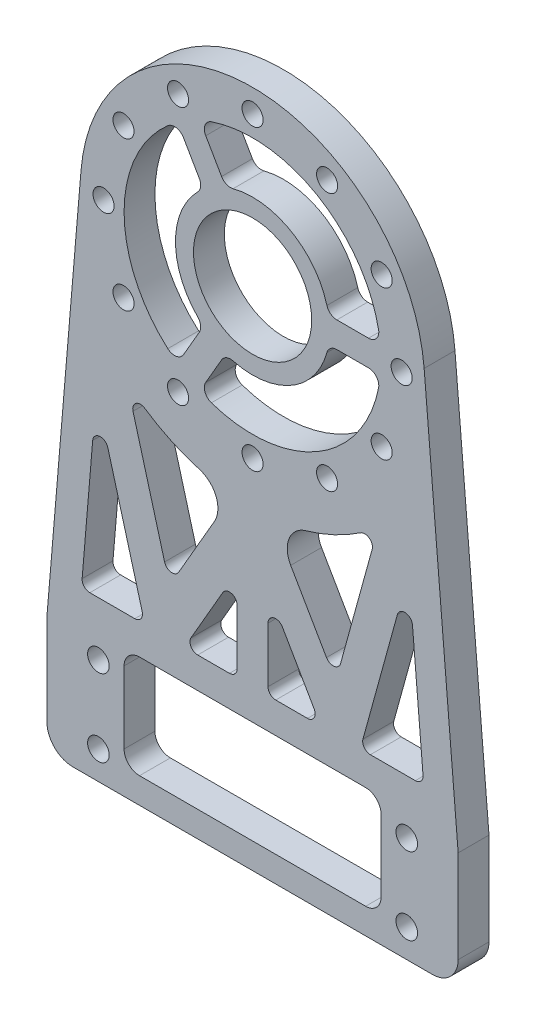
SolidWorks part; units mm, degrees
material "Thornel Mat VMA"
ref_plane "前视基准面" through (0, 0, 0) normal (0, 0, 1) x (1, 0, 0)
ref_plane "上视基准面" through (0, 0, 0) normal (0, 1, 0) x (1, 0, 0)
ref_plane "右视基准面" through (0, 0, 0) normal (1, 0, 0) x (0, 0, -1)
sketch "草图1" plane through (0, 0, 0) normal (0, 0, 1) x (1, 0, 0)
  line L0 (-40, 10) -> (-33.381, 88.3211)
  line L1 (-40, 10) -> (40, 10)
  line L2 (-40, 10) -> (-40, -10)
  line L3 (-40, -10) -> (40, -10)
  line L4 (40, 10) -> (40, -10)
  line L5 (-40, 10) -> (40, -10) construction
  line L6 (-40, -10) -> (40, 10) construction
  line L7 (-30, 7.5) -> (30, 7.5) construction
  line L8 (-30, 7.5) -> (-30, -7.5) construction
  line L9 (-30, -7.5) -> (30, -7.5) construction
  line L10 (30, 7.5) -> (30, -7.5) construction
  line L11 (-30, 7.5) -> (30, -7.5) construction
  line L12 (-30, -7.5) -> (30, 7.5) construction
  line L13 (33.381, 88.3211) -> (40, 10)
  circle A0 centre (0, 85.5) radius 33.5
  circle A1 centre (-30, -7.5) radius 2.1
  circle A2 centre (30, -7.5) radius 2.1
  circle A3 centre (30, 7.5) radius 2.1
  circle A4 centre (-30, 7.5) radius 2.1
  circle A5 centre (0, 85.5) radius 25
  point P0 (0, 0)
  point P6 (0, 0)
  dimension "D4" = 67
  dimension "D6" = 4.2
  dimension "D9" = 50
  dimension "D1" = 60
  dimension "D2" = 15
  dimension "D3" = 80
  dimension "D5" = 93
  dimension "D7" = 2
  dimension "D8" = 2
extrude "凸台-拉伸1" add sketch "草图1" along normal blind 6 contours A0 A5 | A0 L0 L1 L13 | L4 L1 L2 L3 A4 A3 A2 A1 region at (0, 35.2262, 0) region at (0, 0, 0) region at (0, 118.0525, 0)
sketch "草图3" plane through (0, 0, 6) normal (0, 0, 1) x (1, 0, 0)
  circle A0 centre (0, 85.5) radius 29 construction
  circle A1 centre (0, 114.5) radius 2.05
  circle A2 centre (14.5, 110.6147) radius 2.05
  circle A3 centre (25.1147, 100) radius 2.05
  circle A4 centre (29, 85.5) radius 2.05
  circle A5 centre (25.1147, 71) radius 2.05
  circle A6 centre (14.5, 60.3853) radius 2.05
  circle A7 centre (0, 56.5) radius 2.05
  circle A8 centre (-14.5, 60.3853) radius 2.05
  circle A9 centre (-25.1147, 71) radius 2.05
  circle A10 centre (-29, 85.5) radius 2.05
  circle A11 centre (-25.1147, 100) radius 2.05
  circle A12 centre (-14.5, 110.6147) radius 2.05
  point P29 (0, 85.5)
  dimension "D1" = 58
  dimension "D2" = 4.1
  dimension "D3" = 12
extrude "切除-拉伸1" cut sketch "草图3" against normal through all
sketch "草图4" plane through (0, 0, 6) normal (0, 0, 1) x (1, 0, 0)
  line L1 (-14.6024, 105.7921) -> (-7.7775, 93.9711)
  line L2 (-10.2723, 108.2921) -> (-3.4474, 96.4711)
  line L5 (24.8747, 83) -> (11.225, 83)
  line L6 (24.8747, 88) -> (11.225, 88)
  line L7 (-14.6024, 65.2079) -> (-7.7775, 77.0289)
  line L8 (-10.2723, 62.7079) -> (-3.4474, 74.5289)
  circle A0 centre (0, 85.5) radius 11.5
  arc A1 (-9.5602, 97.0587) -> (-9.5602, 73.9413) centre (0, 85.5) ccw
  circle A2 centre (0, 85.5) radius 25
  arc A3 (14.7902, 88) -> (-5.23, 99.5587) centre (0, 85.5) ccw
  arc A4 (-5.23, 71.4413) -> (14.7902, 83) centre (0, 85.5) ccw
  point P24 (0, 85.5)
  circle M13 centre (0, 85.5) radius 25
  dimension "D1" = 23
  dimension "D2" = 50
  dimension "D6" = 30
  dimension "D3" = 5
  dimension "D5" = 3
extrude "凸台-拉伸2" add sketch "草图4" against normal up to surface (6 mm away) separate body contours A0 L2 L1 M13 | A0 L5 L6 M13 | A0 L7 L8 M13 | L1 A1 L7 A0 | L8 A4 L5 A0 | L6 A3 L2 A0 region at (-9.0917, 101.2472, 6) region at (-11.7634, 85.5, 6) region at (-9.0917, 69.7528, 6) region at (5.8817, 95.6874, 6) region at (18.1833, 85.5, 6) region at (5.8817, 75.3126, 6) up to face at (-23.0647, 71, 0)
combine bodies "组合1" operation type add bodies to combine 108 107
fillet "圆角1" radius 2 12 edges at (14.7902, 88, 3) (-5.23, 99.5587, 3) (24.8747, 88, 3) (-5.23, 71.4413, 3) (14.7902, 83, 3) (24.8747, 83, 3) (-10.2723, 62.7079, 3) (-10.2723, 108.2921, 3) (-9.5602, 73.9413, 3) (-14.6024, 65.2079, 3) (-9.5602, 97.0587, 3) (-14.6024, 105.7921, 3)
sketch "草图5" plane through (0, 0, 6) normal (0, 0, 1) x (1, 0, 0)
  line L1 (-40, -10) -> (40, -10)
  line L2 (-40, -10) -> (-40, -13)
  line L3 (-40, -13) -> (40, -13)
  line L4 (40, -10) -> (40, -13)
  dimension "D1" = 3
extrude "凸台-拉伸3" add sketch "草图5" against normal up to surface (6 mm away) up to face at (7.1078, 73.189, 0)
fillet "圆角2" radius 5 2 edges at (40, -13, 3) (-40, -13, 3)
sketch "草图6" plane through (0, 0, 0) normal (0, 0, -1) x (-1, 0, 0)
  line L0 (-39.3239, 18) -> (39.3239, 18)
  line L1 (-30, 7.5) -> (30, 7.5) construction
  line L2 (-30, 7.5) -> (-30, -7.5) construction
  line L3 (-30, -7.5) -> (30, -7.5) construction
  line L4 (30, 7.5) -> (30, -7.5) construction
  line L5 (-25, 12) -> (25, 12)
  line L6 (-25, 12) -> (-25, -8)
  line L7 (-25, -8) -> (25, -8)
  line L8 (25, 12) -> (25, -8)
  line L9 (-25, 12) -> (25, -8) construction
  line L10 (-25, -8) -> (25, 12) construction
  line L11 (-33.381, 88.3211) -> (-40, 10) construction
  line L12 (40, 10) -> (33.381, 88.3211) construction
  line L13 (16.1676, 26.9969) -> (26.1749, 63.3404)
  line L14 (0, 55) -> (16.1676, 26.9969)
  line L15 (34.0213, 9.4947) -> (27.4023, 87.8158)
  line L16 (34.0213, 9.4947) -> (27.4023, 87.8158)
  line L17 (0, 48) -> (-17.3205, 18)
  line L18 (-27.4023, 87.8158) -> (-34.0213, 9.4947)
  line L19 (-27.4023, 87.8158) -> (-34.0213, 9.4947)
  line L20 (0, 48) -> (17.3205, 18)
  line L21 (17.3205, 18) -> (29.5493, 62.4113)
  line L22 (-17.3205, 18) -> (-29.5493, 62.4113)
  line L23 (0, 55) -> (-16.1676, 26.9969)
  line L24 (-16.1676, 26.9969) -> (-26.1749, 63.3404)
  line L25 (19.2986, 12) -> (32.9237, 61.4821)
  line L26 (0, 41) -> (16.7432, 12)
  line L27 (0, 41) -> (-16.7432, 12)
  line L28 (18.4734, 9.0031) -> (32.9237, 61.4821) construction
  line L29 (0, 41) -> (18.4734, 9.0031) construction
  line L30 (0, 41) -> (-18.4734, 9.0031) construction
  line L31 (-19.2986, 12) -> (-32.9237, 61.4821)
  line L32 (-18.4734, 9.0031) -> (-32.9237, 61.4821) construction
  line L33 (0, 41) -> (0, 18)
  line L34 (-3, 41) -> (-3, 18)
  line L35 (3, 41) -> (3, 18)
  circle A0 centre (0, 85.5) radius 37.5
  point P4 (0, 2)
  dimension "D3" = 75
  dimension "D1" = 20
  dimension "D2" = 50
  dimension "D4" = 6
  dimension "D7" = 60
  dimension "D8" = 60
  dimension "D13" = 2
  dimension "D14" = 25
  dimension "D5" = 6
  dimension "D6" = 6
  dimension "D9" = 3.5
  dimension "D10" = 3.5
  dimension "D11" = 3
  dimension "D12" = 3
extrude "切除-拉伸2" cut sketch "草图6" against normal blind 10 contours L8 L5 L6 L7 | L0 L31 L19 | A0 L24 L23 | A0 L14 L13 | L25 L0 L16 | L34 L27 L0 | L26 L35 L0 region at (6.4264, 23.9346, 0) region at (-6.4264, 23.9346, 0) region at (0, 2, 0) region at (28.2184, 29.4411, 0) region at (14.886, 43.2686, 0) region at (-14.886, 43.2686, 0) region at (-28.2184, 29.4411, 0)
fillet "圆角3" radius 3 4 edges at (25, -8, 3) (-25, 12, 3) (-25, -8, 3) (25, 12, 3)
fillet "圆角4" radius 1.5 16 edges at (-3, 18, 3) (-3, 35.8038, 3) (-13.2791, 18, 3) (13.2791, 18, 3) (3, 35.8038, 3) (3, 18, 3) (-16.1676, 26.9969, 3) (-24.4466, 57.0639, 3) (-33.3025, 18, 3) (-20.9508, 18, 3) (-30.4018, 52.3234, 3) (16.1676, 26.9969, 3) (24.4466, 57.0639, 3) (30.4018, 52.3234, 3) (20.9508, 18, 3) (33.3025, 18, 3)
fillet "圆角5" radius 5 2 edges at (3.9227, 48.2057, 3) (-3.9227, 48.2057, 3)
